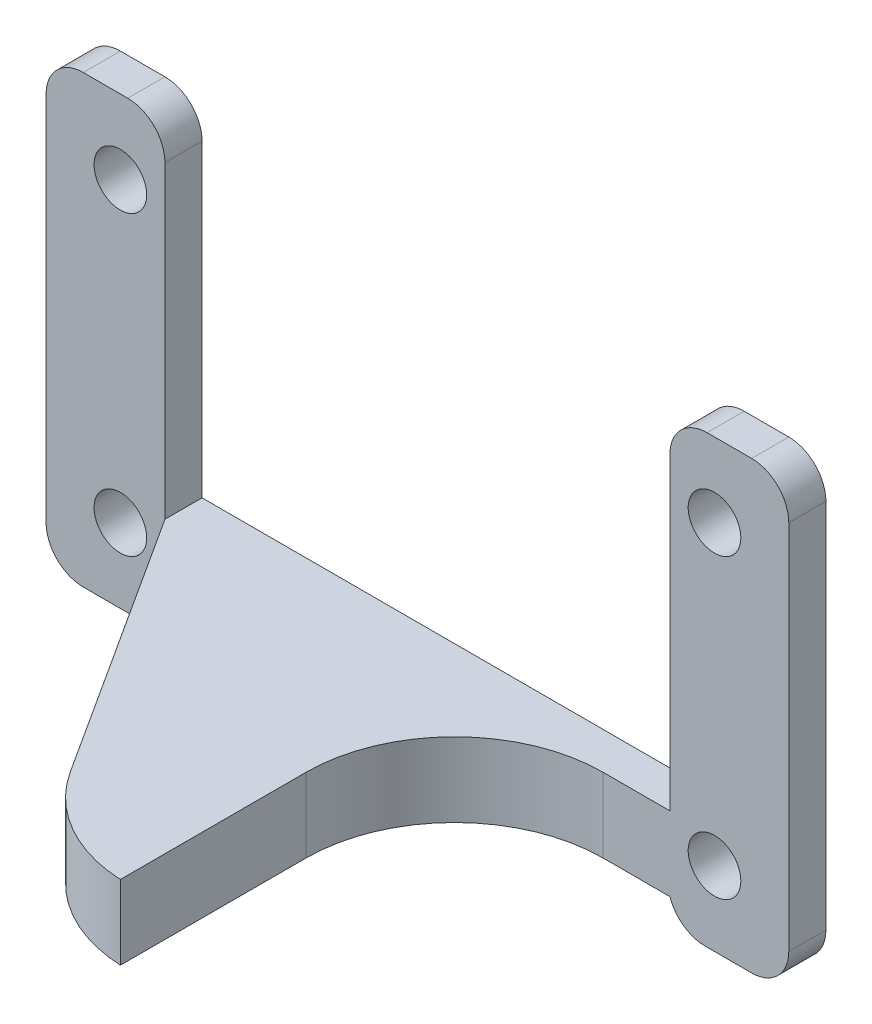
SolidWorks part; units mm, degrees
material "PLA Yellow"
ref_plane "Front" through (0, 0, 0) normal (0, 0, 1) x (1, 0, 0)
ref_plane "Top" through (0, 0, 0) normal (0, 1, 0) x (1, 0, 0)
ref_plane "Right" through (0, 0, 0) normal (1, 0, 0) x (0, 0, -1)
sketch "Sketch1" plane through (0, 0, 0) normal (0, 0, 1) x (1, 0, 0)
  line L1 (-31.75, -19.05) -> (31.75, -19.05)
  line L2 (-31.75, -19.05) -> (-31.75, 19.05)
  line L3 (-31.75, 19.05) -> (31.75, 19.05)
  line L4 (31.75, -19.05) -> (31.75, 19.05)
  line L5 (-31.75, -19.05) -> (31.75, 19.05) construction
  line L6 (-31.75, 19.05) -> (31.75, -19.05) construction
  point P0 (0, 0)
  dimension "D1" = 63.5
  dimension "D2" = 38.1
extrude "Boss-Extrude1" add sketch "Sketch1" along normal blind 3.175
sketch "Sketch2" plane through (0, 0, 3.175) normal (0, 0, 1) x (1, 0, 0)
  line L1 (-21.59, -19.05) -> (21.59, -19.05)
  line L2 (-21.59, -19.05) -> (-21.59, 19.05)
  line L3 (-21.59, 19.05) -> (21.59, 19.05)
  line L4 (21.59, -19.05) -> (21.59, 19.05)
  line L5 (-21.59, -19.05) -> (21.59, 19.05) construction
  line L6 (-21.59, 19.05) -> (21.59, -19.05) construction
  line L7 (-31.75, 19.05) -> (-31.75, -19.05) construction
  line L8 (31.75, 19.05) -> (-31.75, 19.05) construction
  point P0 (0, 0)
  dimension "D2" = 10.16
extrude "Cut-Extrude1" cut sketch "Sketch2" against normal through all
sketch "Sketch3" plane through (0, 0, 0) normal (1, 0, 0) x (0, 0, -1)
  line L5 (-31.75, -10.541) -> (0, -10.541)
  line L6 (-31.75, -10.541) -> (-31.75, -16.891)
  line L7 (-31.75, -16.891) -> (0, -16.891)
  line L8 (0, -10.541) -> (0, -16.891)
  line L9 (-31.75, -10.541) -> (0, -16.891) construction
  line L10 (-31.75, -16.891) -> (0, -10.541) construction
  line L11 (0, -19.05) -> (0, 19.05) construction
  point P6 (-15.875, -13.716)
  dimension "D1" = 6.35
  dimension "D2" = 31.75
  dimension "D3" = 29.591
extrude "Boss-Extrude2" add sketch "Sketch3" along normal mid plane 6.35 contours L6 L7 L5 region at (0, -13.716, 15.875)
sketch "Sketch4" plane through (0, -10.541, 0) normal (0, 1, 0) x (1, 0, 0)
  line L0 (-3.175, -31.75) -> (-21.59, -3.175)
  line L2 (-3.175, 0) -> (-3.175, -31.75)
  line L3 (31.75, -3.175) -> (21.59, -3.175) construction
  line L4 (31.75, 0) -> (21.59, 0) construction
  line L5 (-21.59, -3.175) -> (-21.59, 0)
  line L6 (-21.59, 0) -> (-3.175, 0)
  line L7 (-3.175, -31.75) -> (-3.175, 0) construction
  line L8 (3.175, -31.75) -> (3.175, 0) construction
  line L9 (31.75, 0) -> (3.175, 0)
  line L10 (31.75, 0) -> (31.75, -3.175)
  line L11 (31.75, -3.175) -> (3.175, -3.175)
  line L12 (3.175, 0) -> (3.175, -3.175)
  line L14 (-21.59, -3.175) -> (-31.75, -3.175) construction
extrude "Boss-Extrude3" add sketch "Sketch4" against normal up to surface (6.35 mm away) up to face at (0, -16.891, 15.875)
fillet "Fillet1" radius 12.7 2 edges at (-3.175, -13.716, 31.75) (3.175, -13.716, 3.175)
sketch "Sketch5" plane through (0, 0, 3.175) normal (0, 0, 1) x (1, 0, 0)
  line L0 (-21.59, 19.05) -> (-31.75, 19.05) construction
  line L1 (-25.4, -12.7) -> (25.4, -12.7) construction
  line L2 (-25.4, -12.7) -> (-25.4, 12.7) construction
  line L3 (-25.4, 12.7) -> (25.4, 12.7) construction
  line L4 (25.4, -12.7) -> (25.4, 12.7) construction
  line L5 (-25.4, -12.7) -> (25.4, 12.7) construction
  line L6 (-25.4, 12.7) -> (25.4, -12.7) construction
  line L7 (-31.75, 19.05) -> (-31.75, -19.05) construction
  circle A0 centre (-25.4, 12.7) radius 2.25
  circle A1 centre (-25.4, -12.7) radius 2.25
  circle A2 centre (25.4, -12.7) radius 2.25
  circle A3 centre (25.4, 12.7) radius 2.25
  point P0 (0, 0)
  dimension "D3" = 4.5
  dimension "D1" = 6.35
  dimension "D2" = 6.35
extrude "Cut-Extrude2" cut sketch "Sketch5" against normal through all
fillet "Fillet2" radius 3.175 8 edges at (21.59, 19.05, 1.5875) (31.75, 19.05, 1.5875) (31.75, -19.05, 1.5875) (21.59, -19.05, 1.5875) (-31.75, -19.05, 1.5875) (-21.59, -19.05, 1.5875) (-21.59, 19.05, 1.5875) (-31.75, 19.05, 1.5875)
